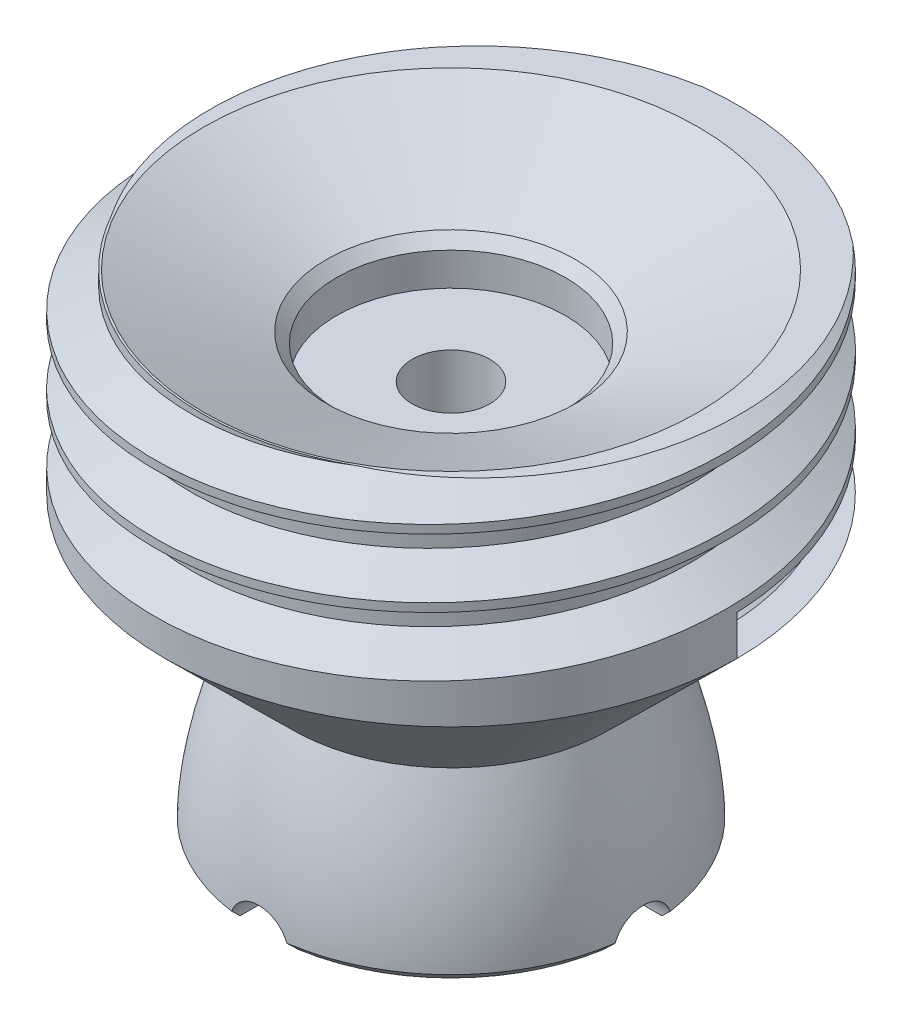
SolidWorks part; units mm, degrees
ref_plane "Front Plane" through (0, 0, 0) normal (0, 0, 1) x (1, 0, 0)
ref_plane "Top Plane" through (0, 0, 0) normal (0, 1, 0) x (1, 0, 0)
ref_plane "Right Plane" through (0, 0, 0) normal (1, 0, 0) x (0, 0, -1)
sketch "Sketch1" plane through (0, 0, 0) normal (0, 1, 0) x (1, 0, 0)
  circle A0 centre (0, 0) radius 14.75
  dimension "D1" = 29.5
extrude "Boss-Extrude1" add sketch "Sketch1" along normal blind 10
sketch "Sketch2" plane through (0, 0, 0) normal (0, 0, 1) x (1, 0, 0)
  line L0 (0, 0) -> (0, 14.0598) construction
  line L1 (-12.75, 10) -> (-5.9, 7)
  line L2 (14.75, 10) -> (-14.75, 10) construction
  line L3 (-5.9, 7) -> (-5.9, 5)
  line L4 (-5.9, 5) -> (-2, 5)
  line L5 (-2, 5) -> (-2, 0)
  line L6 (-14.75, 0) -> (14.75, 0) construction
  line L7 (-2, 0) -> (0, 0)
  line L8 (0, 0) -> (0, 10)
  line L9 (0, 10) -> (-12.75, 10)
  line L10 (-14.75, 10) -> (-14.75, 0) construction
  dimension "D1" = 2
  dimension "D2" = 2
  dimension "D3" = 5.9
  dimension "D4" = 2
  dimension "D5" = 5
revolve "Cut-Revolve1" cut sketch "Sketch2" angle 360 about L0
chamfer "Chamfer1" distance 0.3 angle 45 1 edges at (0, 7, -5.9)
sketch "Sketch3" plane through (0, 0, 0) normal (0, 0, 1) x (1, 0, 0)
  line L0 (0, 0) -> (0, -21.0187) construction
  line L1 (0, -14.9282) -> (-18.6982, -14.9282) construction
  line L2 (-2, -8.5093) -> (-2, 8.5093) construction
  line L3 (-6, -30.1317) -> (-6, -12.8537) construction
  line L6 (-2, 0) -> (-6, 0)
  line L7 (-2, 0) -> (-6, -14.9282) construction
  line L8 (-6, -14.9282) -> (-10, -14.9282)
  line L9 (-2, 0) -> (-2, -13.9036) construction
  spline S0 degree 3 poles (-2, 0) (-2, -3.767) (-6, -9.4528) (-6, -14.9282) knots 0 0 0 0 1 1 1 1
  spline S1 degree 1 poles (-6, 0) (-10, -14.9282) knots 0 0 1 1 construction
  spline S2 degree 3 poles (-6, 0) (-6, -0.0366) (-6.002, -0.0993) (-6.0199, -0.3089) (-6.077, -0.6621) (-6.2135, -1.224) (-6.4852, -2.1186) (-6.9765, -3.4632) (-7.9676, -5.9672) (-9.069, -8.8919) (-9.7364, -11.7936) (-9.9577, -13.5479) (-10, -14.4715) (-10, -14.9282) knots 0 0 0 0 0.03125 0.0625 0.125 0.1875 0.25 0.375 0.5 0.75 0.875 0.9375 1 1 1 1
  dimension "D2" = 6
  dimension "D1" = 15
  dimension "D3" = 4
revolve "Revolve1" add sketch "Sketch3" angle 360 about L0
thread "Thread1" pitch 3.5 start angle 0, offset 1, length 10, pitch 3.5, diameter 29.5
ref_plane "Plane1" through (14.75, -1, 0) normal (0, 0, 1) x (1, 0, 0)
sketch "Thread Profile1" plane through (14.75, -1, 0) normal (0, 0, 1) x (1, 0, 0)
  line L0 (0, 0) -> (0, 3.5) construction
  line L11 (0, 0) -> (0, 3.0625)
  line L12 (0, 3.0625) -> (-1.8944, 1.9687)
  line L13 (-1.8944, 1.9687) -> (-1.8944, 1.0937)
  line L15 (-1.8944, 1.0937) -> (0, 0)
  line L17 (-1.8944, 1.5312) -> (0, 1.5312) construction
  point P2 (0, 0)
  dimension "Pitch" = 3.5
  dimension "Profile_Angle" = 60
  dimension "Profile_Land" = 0.875
  dimension "Profile_Height" = 1.8944
sketch "Sketch6" plane through (0, 0, 0) normal (0, 0, 1) x (1, 0, 0)
  line L1 (0, 0) -> (0, -34.079) construction
  line L2 (-10, -14.9282) -> (10, -14.9282) construction
  circle A0 centre (0, -14.9282) radius 1.5
  dimension "D1" = 3
extrude "Cut-Extrude1" cut sketch "Sketch6" against normal blind 10
pattern_circular "CirPattern1" count 4 over 360 about axis through (0, 0, 0) along (0, -1, 0) of "Cut-Extrude1"
sketch "Sketch7" plane through (0, 0, 0) normal (0, 0, 1) x (1, 0, 0)
  line L0 (-14.75, 0) -> (-8.1564, -6.4936)
  line L1 (-14.75, 0) -> (-6, 0)
  spline S0 degree 3 poles (35.2048, 999.1506) (-8.6275, -13.9308) (-5.8256, 1.9667) (-6.0199, -0.3089) (-6.077, -0.6621) (-6.2135, -1.224) (-6.4852, -2.1186) (-6.9765, -3.4632) (-7.9676, -5.9672) (-9.069, -8.8919) (-14.8067, -33.8409) (21.9289, -82.4589) (693.6761, -724.0073) knots -1.232448 -1.232448 -1.232448 -1.232448 0.03125 0.0625 0.125 0.1875 0.25 0.375 0.5 0.75 0.875 4.261703 4.261703 4.261703 4.261703 only from (-6, 0) to (-9.9289, -13.4282) construction
  spline S1 degree 3 poles (-6, 0) (-6, -0.0366) (-6.002, -0.0993) (-6.0199, -0.3089) (-6.077, -0.6621) (-6.2135, -1.224) (-6.4852, -2.1186) (-6.9765, -3.4632) (-7.6077, -5.058) (-8.0132, -6.1108) (-8.1564, -6.4936) knots 0 0 0 0 0.03125 0.0625 0.125 0.1875 0.25 0.375 0.5 0.568451 0.568451 0.568451 0.568451
revolve "Revolve2" add sketch "Sketch7" angle 360
chamfer "Chamfer2" distance 0.5 angle 45 4 edges at (7.0711, -14.9282, -7.0711) (-7.0711, -14.9282, -7.0711) (-7.0711, -14.9282, 7.0711) (7.0711, -14.9282, 7.0711)
equation "\"InsideDia\" = 29.5"
equation "\"D1@Sketch1\"=\"InsideDia\""
